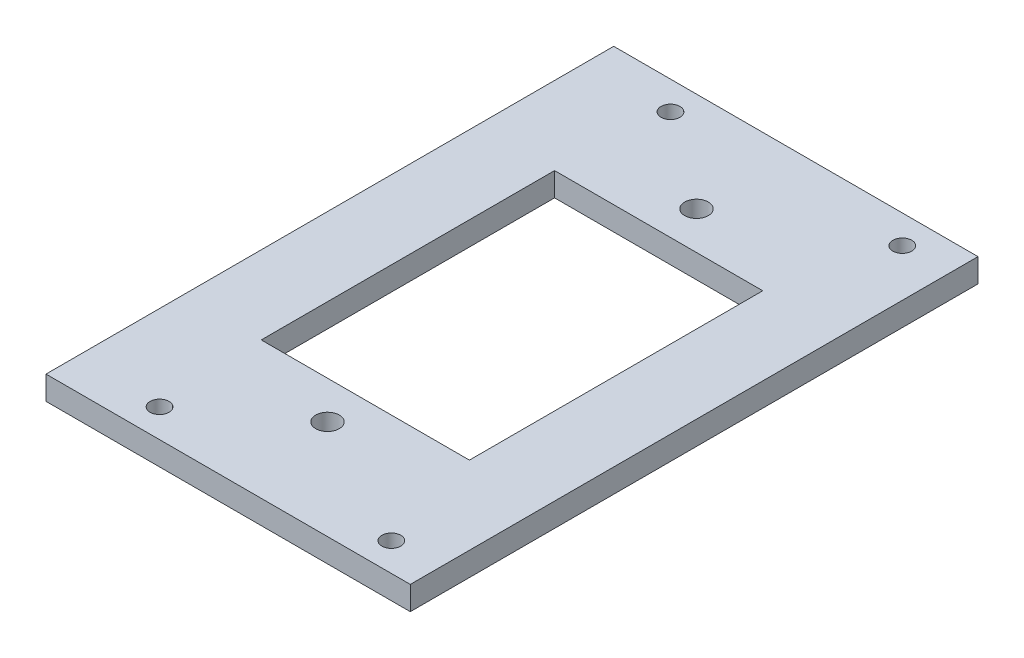
SolidWorks part; units mm, degrees
ref_plane "前视基准面" through (0, 0, 0) normal (0, 0, 1) x (1, 0, 0)
ref_plane "上视基准面" through (0, 0, 0) normal (0, 1, 0) x (1, 0, 0)
ref_plane "右视基准面" through (0, 0, 0) normal (1, 0, 0) x (0, 0, -1)
sketch "草图1" plane through (0, 0, 0) normal (0, 1, 0) x (1, 0, 0)
  line L0 (38.5, -77) -> (38.5, 77) construction
  line L1 (-38.5, 60) -> (38.5, 60)
  line L2 (-38.5, 60) -> (-38.5, -60)
  line L3 (-38.5, -60) -> (38.5, -60)
  line L4 (38.5, 60) -> (38.5, -60)
  line L5 (0, -60) -> (0, 60) construction
  line L6 (-38.5, 0) -> (38.5, 0) construction
  line L8 (22, 31) -> (-22, 31)
  line L9 (22, 31) -> (22, -31)
  line L10 (22, -31) -> (-22, -31)
  line L11 (-22, 31) -> (-22, -31)
  line L12 (0, -31) -> (0, 31) construction
  line L13 (22, 0) -> (-22, 0) construction
  circle A0 centre (0, 39) radius 2.5
  circle A1 centre (0, -39) radius 2.5
  point P1 (0, 0)
  point P7 (0, 0)
  dimension "D2" = 44
  dimension "D6" = 5
  dimension "D1" = 120
  dimension "D3" = 62
  dimension "D7" = 78
extrude "凸台-拉伸1" add sketch "草图1" along normal blind 5
hole_wizard "大小mm Clearance 暗销孔0" positions "草图5" profile "草图6" hole size "Ø4.0" standard "GB" end condition through all
sketch "草图5" plane through (0, 0, 0) normal (0, -1, 0) x (-1, 0, 0)
  line L3 (-38.5, -60) -> (-38.5, 60) construction
  line L5 (-38.5, 60) -> (38.5, 60) construction
  line L6 (38.5, 60) -> (38.5, -60) construction
  point P0 (-28.5, 54)
  point P19 (20.5, 54)
  dimension "D1" = 10
  dimension "D2" = 6
  dimension "D3" = 18
sketch "草图6" plane through (28.5, 0, -54) normal (1, 0, 0) x (0, 0, -1)
  line L0 (0, 0) -> (0, 5)
  line L1 (0, 5) -> (2, 5)
  line L2 (2, 5) -> (2, 0)
  line L5 (2, 0) -> (0, 0)
  line L11 (0, -6.35) -> (0, 107.95) construction
  dimension "通孔孔直径" = 4
  dimension "通孔孔深度" = 5
mirror "镜向1" about plane through (0, 0, 0) normal (0, 0, 1) of "大小mm Clearance 暗销孔0"
